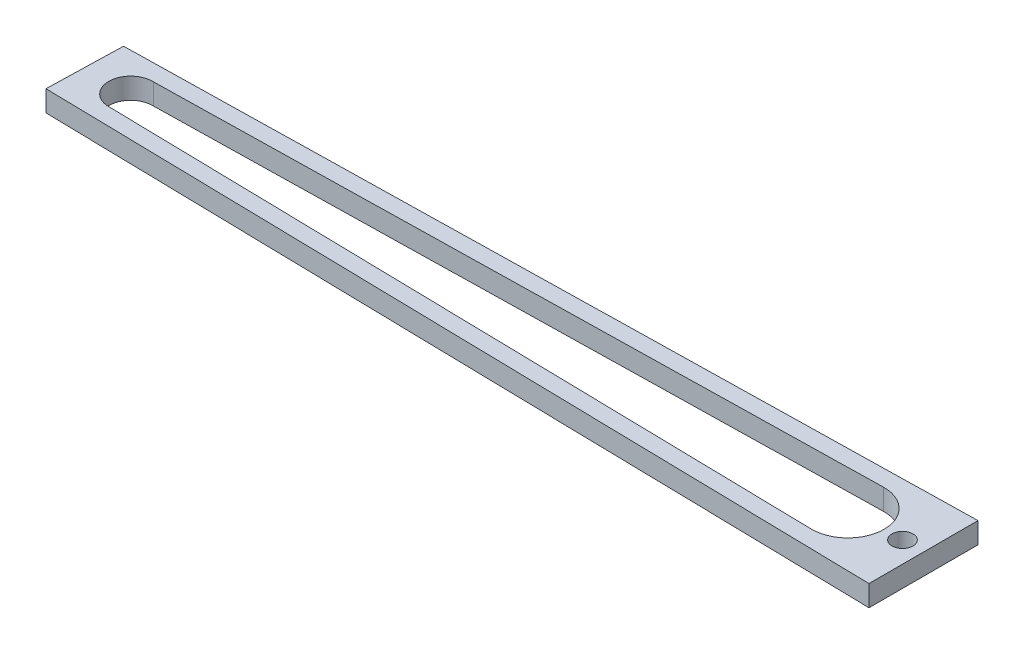
SolidWorks part; units mm, degrees
ref_plane "Front Plane" through (0, 0, 0) normal (0, 0, 1) x (1, 0, 0)
ref_plane "Top Plane" through (0, 0, 0) normal (0, 1, 0) x (1, 0, 0)
ref_plane "Right Plane" through (0, 0, 0) normal (1, 0, 0) x (0, 0, -1)
sketch "Sketch1" plane through (0, 0, 0) normal (0, 1, 0) x (1, 0, 0)
  line L29 (-90.0051, -41.9994) -> (-90.48, -59.9931)
  line L30 (-90.48, -59.9931) -> (109.52, -64.0568)
  line L31 (109.52, -64.0568) -> (109.52, -38.0977)
  line L32 (109.52, -38.0977) -> (-90.0051, -41.9994)
  line L33 (-90.2426, -50.9963) -> (109.52, -51.0772) construction
  line L34 (-58.6749, -44.2523) -> (-58.6777, -51.0091) construction
  line L48 (-49.8078, -41.272) -> (-49.8078, -41.2133)
  line L51 (-30.1907, -57.2108) -> (-30.3693, -57.2046)
  line L55 (91.3515, -42.4538) -> (-79.7182, -45.799)
  line L57 (91.3445, -59.686) -> (-79.4193, -56.217)
  line L58 (105.52, -42.1767) -> (-86.1073, -45.9239) construction
  line L59 (-86.1073, -45.9239) -> (-86.3752, -56.0757) construction
  line L60 (-86.3752, -56.0757) -> (105.52, -59.9747) construction
  line L61 (105.52, -59.9747) -> (105.52, -42.1767) construction
  circle A16 centre (104.52, -51.0752) radius 2.5
  arc A17 (78.0382, -58.2384) -> (78.1222, -58.2389) centre (78.1233, -51.0645) ccw
  arc A20 (78.169, -43.8903) -> (78.0833, -43.8902) centre (78.1233, -51.0645) ccw
  arc A22 (91.3445, -59.686) -> (91.3515, -42.4538) centre (91.52, -51.0699) ccw
  arc A24 (-30.3693, -57.2046) -> (-30.1907, -57.2108) centre (-30.0646, -51.0207) ccw
  arc A25 (-79.1122, -45.7872) -> (-79.4193, -56.217) centre (-79.3133, -51.0007) ccw
  point P1 (-48.8078, -41.272)
  point P4 (-48.8078, -60.7586)
  point P5 (105.52, -42.1767)
  point P7 (-86.1073, -45.9239)
  point P9 (-86.3752, -56.0757)
  point P10 (105.52, -59.9747)
  point P42 (-54.2997, -51.0083)
  point P45 (-88.7503, -50.9975)
  point P65 (94.6498, -46.8901)
  point P66 (-87.0785, -45.8643)
  point P67 (-87.396, -57.8974)
  point P68 (94.6498, -60.8578)
  point P70 (-49.8078, -60.7586)
  dimension "D8" = 5
  dimension "D9" = 5
  dimension "D1" = 200
  dimension "D2" = 4
  dimension "D5" = 18
extrude "Boss-Extrude1" add sketch "Sketch1" along normal blind 5 contours L31 L32 L29 L30 A25 L55 A22 L57 A16 region at (-69.867, 0, 43.6228)
